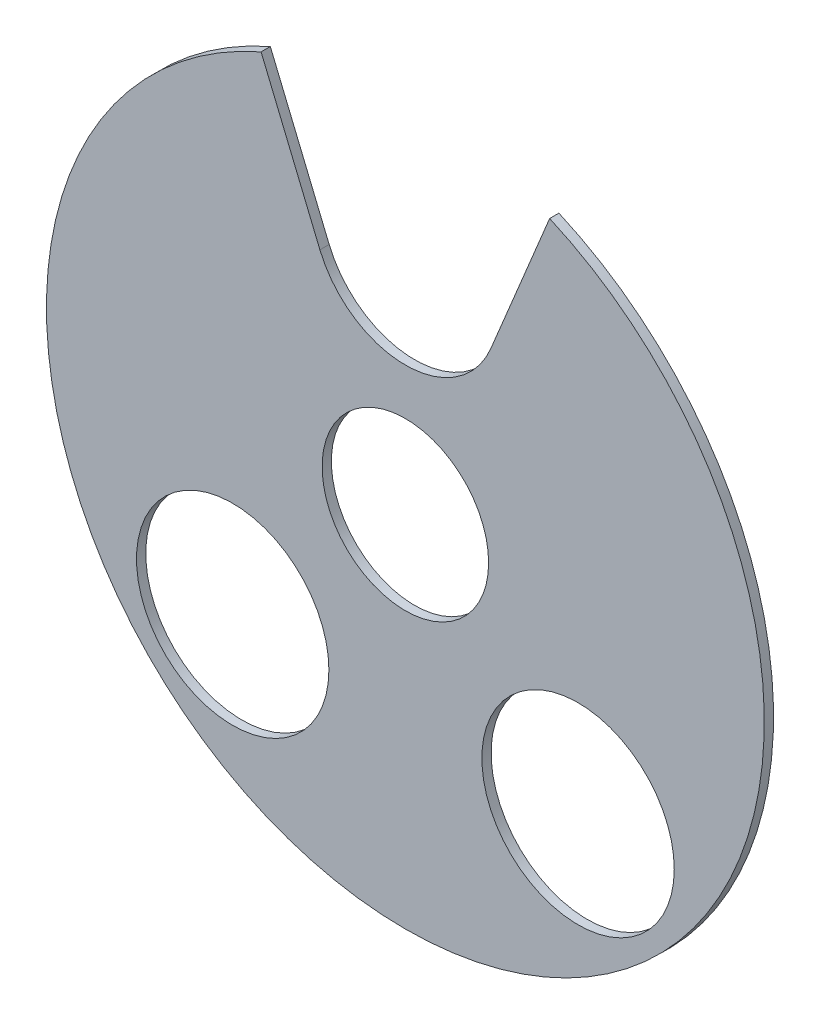
SolidWorks part; units mm, degrees
ref_plane "Front Plane" through (0, 0, 0) normal (0, 0, 1) x (1, 0, 0)
ref_plane "Top Plane" through (0, 0, 0) normal (0, 1, 0) x (1, 0, 0)
ref_plane "Right Plane" through (0, 0, 0) normal (1, 0, 0) x (0, 0, -1)
sketch "Esquisse1" plane through (0, 0, 0) normal (0, 0, 1) x (1, 0, 0)
  circle A0 centre (0, 0) radius 97
  circle A1 centre (0, 0) radius 22.5
  dimension "D1" = 194
  dimension "D2" = 45
extrude "Main" add sketch "Esquisse1" along normal blind 2.5
sketch "Esquisse2" plane through (0, 0, 2.5) normal (0, 0, 1) x (1, 0, 0)
  line L0 (-23.097, 50.4329) -> (-38.9959, 88.8162)
  line L1 (23.097, 50.4329) -> (38.9959, 88.8162)
  line L2 (0, 0) -> (0, -112.8607) construction
  line L3 (-46.669, -46.669) -> (0, 0) construction
  arc A0 (-23.097, 50.4329) -> (23.097, 50.4329) centre (0, 60) ccw
  circle A1 centre (0, 0) radius 97 construction
  circle A2 centre (-46.669, -46.669) radius 26
  circle A3 centre (46.669, -46.669) radius 26
  arc A4 (-38.9959, 88.8162) -> (38.9959, 88.8162) centre (0, 0) cw
  dimension "D2" = 25
  dimension "D4" = 52
  dimension "D1" = 45
  dimension "D3" = 60
  dimension "D5" = 45
  dimension "D6" = 90
  dimension "D7" = 66
extrude "Holes" cut sketch "Esquisse2" against normal through all and the other way through all
